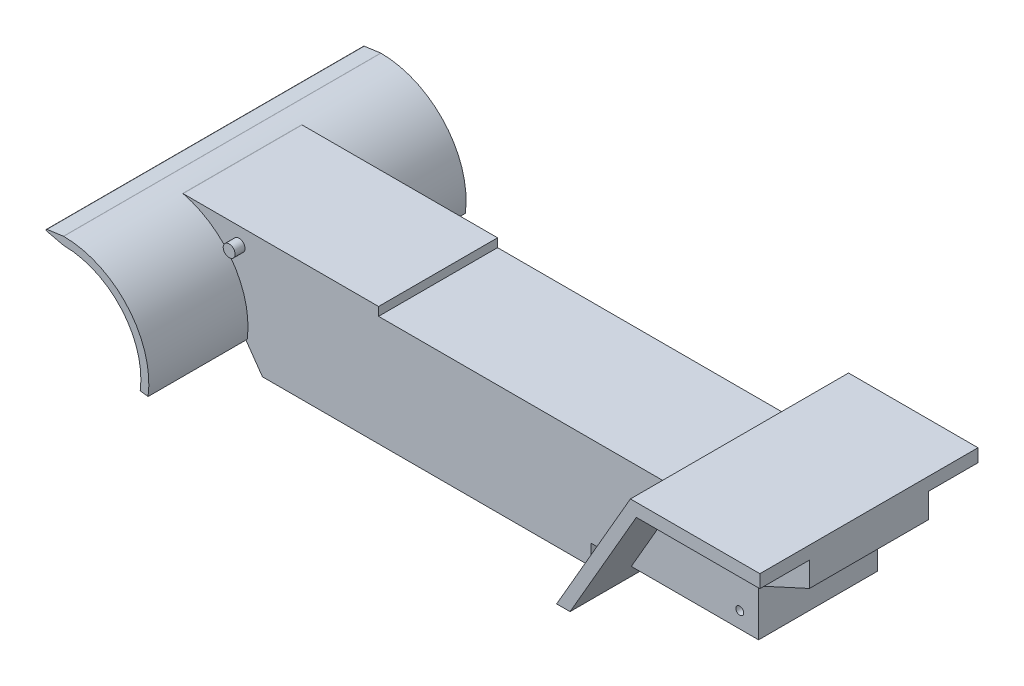
SolidWorks part; units mm, degrees
ref_plane "Front Plane" through (0, 0, 0) normal (0, 0, 1) x (1, 0, 0)
ref_plane "Top Plane" through (0, 0, 0) normal (0, 1, 0) x (1, 0, 0)
ref_plane "Right Plane" through (0, 0, 0) normal (1, 0, 0) x (0, 0, -1)
sketch "Sketch1" plane through (0, 0, 0) normal (0, 0, 1) x (1, 0, 0)
  line L0 (0, 462.9869) -> (7112, 462.9869) construction
  line L1 (0, 0) -> (5713.2841, 0)
  line L2 (0, 0) -> (0, 1524)
  line L3 (0, 1524) -> (8509, 1524)
  line L4 (8509, 1155.4795) -> (8509, 1524)
  line L5 (0, 644.7339) -> (1051.2961, 644.7339)
  line L6 (1051.2961, 644.7339) -> (1502.7319, 0)
  line L7 (8509, 1155.4795) -> (7857.5524, 856.8781)
  line L8 (0, 644.7339) -> (468.6132, 644.7339)
  line L9 (0, 644.7339) -> (0, 288.6393)
  line L10 (0, 288.6393) -> (468.6132, 288.6393)
  line L11 (468.6132, 644.7339) -> (468.6132, 288.6393)
  line L12 (7857.5524, 856.8781) -> (7857.5524, 259.2417)
  line L13 (7857.5524, 259.2417) -> (5713.2841, 259.2417)
  line L14 (5713.2841, 259.2417) -> (5713.2841, 0)
  circle A0 centre (224.995, 462.9869) radius 50.8
  circle A1 centre (7616.395, 462.9869) radius 50.8
  dimension "D3" = 7391.4
  dimension "D1" = 8509
  dimension "D2" = 1524
extrude "Boss-Extrude1" add sketch "Sketch1" along normal blind 1524 contours L0 L2 L5 L6 L1 L4 A1 A0 | L2 L0 A0 A1 L4 L3 | L9 L8 L11 L10 | A0 region at (234.7927, 372.3877, 0) region at (4158.5522, 844.2747, 0)
sketch "Sketch2" plane through (0, 0, 1524) normal (0, 0, 1) x (1, 0, 0)
  line L0 (1206.8624, 331.7439) -> (1307.5668, 318.2831)
  line L1 (224.995, 1555.1869) -> (224.995, 1453.5869)
  circle A0 centre (224.995, 462.9869) radius 635 construction
  circle A2 centre (7616.395, 462.9869) radius 1270 construction
  arc A4 (1206.8624, 331.7439) -> (224.995, 1453.5869) centre (224.995, 462.9869) ccw
  arc A5 (1307.5668, 318.2831) -> (224.995, 1555.1869) centre (224.995, 462.9869) ccw
  dimension "D1" = 990.6
  dimension "D2" = 1092.2
extrude "Boss-Extrude2" add sketch "Sketch2" along normal blind 1270 and the other way blind 2794
sketch "Sketch3" plane through (0, 0, 1524) normal (0, 0, 1) x (1, 0, 0)
  line L0 (5905.6386, 0) -> (6850.7783, 1637.03)
  line L1 (6850.7783, 1637.03) -> (8509, 1637.03)
  line L2 (5905.6386, 0) -> (6077.7387, 0)
  line L3 (6077.7387, 0) -> (6926.6919, 1470.43)
  line L4 (6926.6919, 1470.43) -> (8509, 1470.43)
  line L5 (8509, 1637.03) -> (8509, 1470.43)
  line L6 (1502.7319, 0) -> (5713.2841, 0) construction
  line L7 (6077.7387, 0) -> (6934.0391, 0) construction
  circle A0 centre (7616.395, 462.9869) radius 635
  dimension "D1" = 60
  dimension "D2" = 1637.03
extrude "Boss-Extrude3" add sketch "Sketch3" along normal blind 635 and the other way blind 2159 contours L5 L4 L3 L2 L0 L1
sketch "Sketch4" plane through (0, 0, 1524) normal (0, 0, 1) x (1, 0, 0)
  line L6 (2989.867, 1414.4778) -> (6785.5204, 1414.4778)
  line L7 (2989.867, 1414.4778) -> (2989.867, 1524)
  line L8 (2989.867, 1524) -> (6785.5204, 1524)
  line L9 (6785.5204, 1414.4778) -> (6785.5204, 1524)
sketch "Sketch5" plane through (0, 0, 1524) normal (0, 0, 1) x (1, 0, 0)
  circle A0 centre (1202.8434, 1311.7191) radius 76.2
extrude "Boss-Extrude5" add sketch "Sketch5" along normal blind 127 and the other way blind 1651
sketch "Sketch7" plane through (0, 0, 2794) normal (0, 0, 1) x (1, 0, 0)
  line L0 (224.995, 1555.1869) -> (0, 1524)
  line L1 (0, 1524) -> (224.995, 1524)
  line L2 (224.995, 1524) -> (224.995, 1555.1869)
extrude "Boss-Extrude6" add sketch "Sketch7" against normal through all
sketch "Sketch8" plane through (0, 0, 2794) normal (0, 0, 1) x (1, 0, 0)
  line L0 (0, 1506.7726) -> (224.995, 1453.5869)
  line L1 (0, 288.6393) -> (0, 1524) construction
  line L2 (224.995, 1453.5869) -> (224.995, 1524)
  line L3 (224.995, 1524) -> (0, 1524)
  line L4 (0, 1524) -> (0, 1506.7726)
extrude "Boss-Extrude7" add sketch "Sketch8" against normal through all
fillet "Fillet1" radius 20.32 1 edges at (224.995, 1555.1869, 762)
fillet "Fillet2" radius 15.24 1 edges at (0, 1524, 762)
fillet "Fillet3" radius 15.24 1 edges at (484.1321, 1524, 762)
fillet "Fillet4" radius 15.24 1 edges at (0, 1506.7726, 2159)
fillet "Fillet5" radius 15.24 1 edges at (0, 1506.7726, -635)
extrude "Cut-Extrude1" cut sketch "Sketch4" against normal blind 1524
